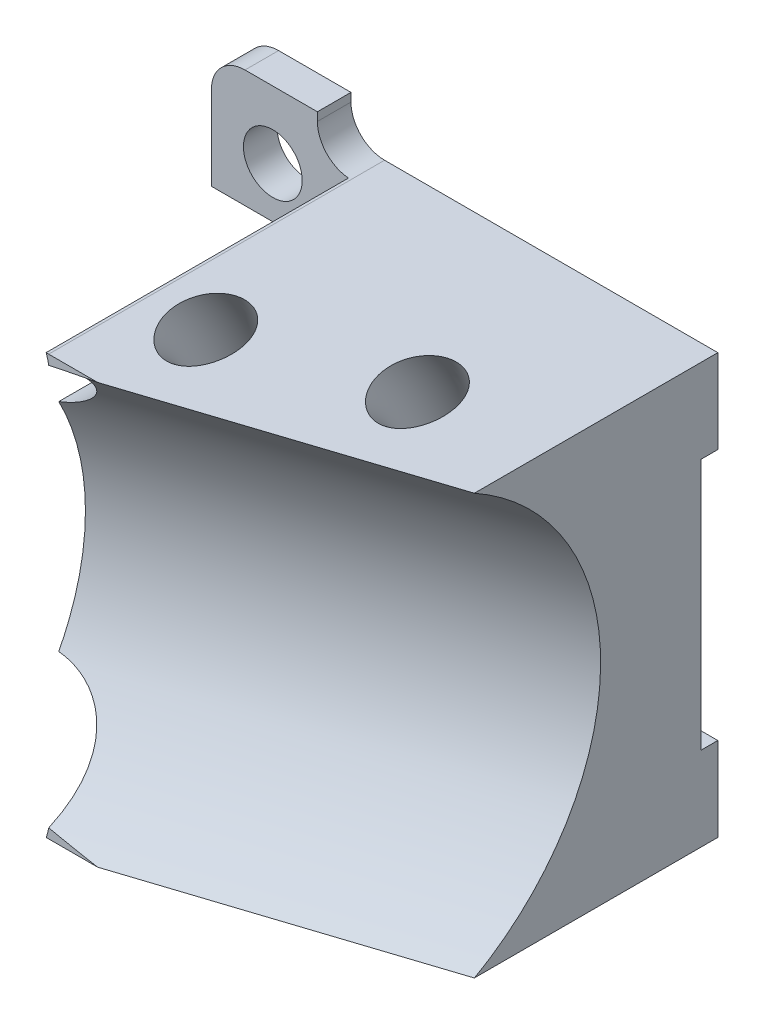
SolidWorks part; units mm, degrees
ref_plane "Front Plane" through (0, 0, 0) normal (0, 0, 1) x (1, 0, 0)
ref_plane "Top Plane" through (0, 0, 0) normal (0, 1, 0) x (1, 0, 0)
ref_plane "Right Plane" through (0, 0, 0) normal (1, 0, 0) x (0, 0, -1)
sketch "Sketch1" plane through (0, 0, 0) normal (0, 0, 1) x (1, 0, 0)
  line L1 (-12.5, 12.5) -> (12.5, 12.5)
  line L2 (-12.5, 12.5) -> (-12.5, -12.5)
  line L3 (-12.5, -12.5) -> (12.5, -12.5)
  line L4 (12.5, 12.5) -> (12.5, -12.5)
  line L5 (-12.5, 12.5) -> (12.5, -12.5) construction
  line L6 (-12.5, -12.5) -> (12.5, 12.5) construction
  point P0 (0, 0)
  dimension "D1" = 25
  dimension "D2" = 25
extrude "Boss-Extrude1" add sketch "Sketch1" along normal blind 20
ref_plane "Plane1" through (11.3064, 0, -3.6737) normal (0.9511, 0, -0.309) x (0, 1, 0)
sketch "Sketch2" plane through (11.3064, 0, -3.6737) normal (0.9511, 0, -0.309) x (0, 1, 0)
  line L0 (0, 25) -> (0, 0) construction
  circle A0 centre (0, 25) radius 14.5
  dimension "D1" = 29
  dimension "D2" = 25
extrude "Cut-Extrude1" cut sketch "Sketch2" against normal through all
sketch "Sketch3" plane through (0, 0, 0) normal (0, 0, 1) x (1, 0, 0)
  line L0 (-12.5, 10.6486) -> (-12.5, -10.6486) construction
  line L1 (-15.6552, 15) -> (-9.3448, 15)
  line L2 (-15.6552, 15) -> (-15.6552, -15)
  line L3 (-15.6552, -15) -> (-9.3448, -15)
  line L4 (-9.3448, 15) -> (-9.3448, -15)
  line L5 (-15.6552, 15) -> (-9.3448, -15) construction
  line L6 (-15.6552, -15) -> (-9.3448, 15) construction
  point P0 (-12.5, 0)
  dimension "D1" = 30
extrude "Boss-Extrude2" add sketch "Sketch3" along normal blind 2
sketch "Sketch4" plane through (0, 0, 0) normal (0, 0, 1) x (1, 0, 0)
  line L0 (-15.6552, 15) -> (-15.6552, -15) construction
  line L1 (-20.6552, 8) -> (-10.6552, 8)
  line L2 (-20.6552, 8) -> (-20.6552, -8)
  line L3 (-20.6552, -8) -> (-10.6552, -8)
  line L4 (-10.6552, 8) -> (-10.6552, -8)
  line L5 (-20.6552, 8) -> (-10.6552, -8) construction
  line L6 (-20.6552, -8) -> (-10.6552, 8) construction
  point P0 (-15.6552, 0)
  dimension "D1" = 16
  dimension "D2" = 5
extrude "Cut-Extrude2" cut sketch "Sketch4" along normal through all
sketch "Sketch5" plane through (0, 0, 2) normal (0, 0, 1) x (1, 0, 0)
  line L0 (-12, 11) -> (-12, -11) construction
  line L1 (-12, 0) -> (0, 0) construction
  circle A0 centre (-12, 11) radius 1.75
  circle A1 centre (-12, -11) radius 1.75
  dimension "D3" = 3.5
  dimension "D1" = 12
  dimension "D2" = 22
extrude "Cut-Extrude3" cut sketch "Sketch5" against normal through all both and the other way through all
sketch "Sketch7" plane through (0, 0, 2) normal (0, 0, 1) x (1, 0, 0)
  circle A2 centre (-12, 11) radius 4.75
  circle A3 centre (-12, 11) radius 4.75
  circle A5 centre (-12, -11) radius 4.75
  circle A6 centre (-12, -11) radius 4.75
  dimension "D1" = 3
  dimension "D2" = 3
extrude "Cut-Extrude4" cut sketch "Sketch7" along normal through all
ref_plane "Plane2" through (1.7958, 0, -0.5835) normal (0.9511, 0, -0.309) x (0, 1, 0)
sketch "Sketch8" plane through (1.7958, 0, -0.5835) normal (0.9511, 0, -0.309) x (0, 1, 0)
  circle A0 centre (0, 25) radius 18
  dimension "D1" = 36
sweep "Cut-Sweep1" cut path "Sketch8" circular profile diameter 4 parameters "D3"=4
pattern_linear "LPattern1" count 2 spacing 10 along (-0.9511, 0, 0.309) of "Cut-Sweep1"
fillet "Fillet1" radius 2 4 edges at (-9.3448, 12.5, 1) (-9.3448, -12.5, 1) (-15.6552, -15, 1) (-15.6552, 15, 1)
sketch "Sketch11" plane through (12.5, 0, 0) normal (1, 0, 0) x (0, 0, -1)
  line L1 (-1, 7.5) -> (1, 7.5)
  line L2 (-1, 7.5) -> (-1, -7.5)
  line L3 (-1, -7.5) -> (1, -7.5)
  line L4 (1, 7.5) -> (1, -7.5)
  line L5 (-1, 7.5) -> (1, -7.5) construction
  line L6 (-1, -7.5) -> (1, 7.5) construction
  dimension "D1" = 15
  dimension "D2" = 2
extrude "Cut-Extrude5" cut sketch "Sketch11" against normal through all
